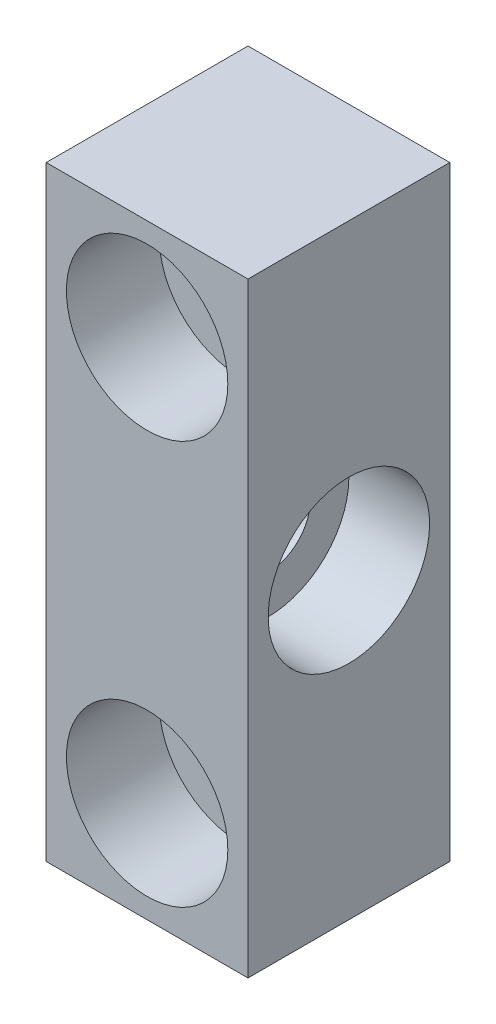
SolidWorks part; units mm, degrees
material "6061 合金"
ref_plane "前视基准面" through (0, 0, 0) normal (0, 0, 1) x (1, 0, 0)
ref_plane "上视基准面" through (0, 0, 0) normal (0, 1, 0) x (1, 0, 0)
ref_plane "右视基准面" through (0, 0, 0) normal (1, 0, 0) x (0, 0, -1)
sketch "草图1" plane through (0, 0, 0) normal (0, 0, 1) x (1, 0, 0)
  line L1 (-5, -15) -> (5, -15)
  line L2 (-5, -15) -> (-5, 15)
  line L3 (-5, 15) -> (5, 15)
  line L4 (5, -15) -> (5, 15)
  line L5 (-5, -15) -> (5, 15) construction
  line L6 (-5, 15) -> (5, -15) construction
  point P0 (0, 0)
  dimension "D1" = 10
  dimension "D2" = 30
extrude "凸台-拉伸1" add sketch "草图1" along normal blind 10
hole_wizard "打孔尺寸(%根据)内六角圆柱头螺钉的类型1" positions "草图3" profile "草图2" counterbore size "M4" standard "GB" end condition through all
sketch "草图3" plane through (0, 0, 10) normal (0, 0, 1) x (1, 0, 0)
  line L0 (5, 15) -> (-5, 15) construction
  point P0 (0, 10)
  point P2 (0, -10)
  dimension "D1" = 20
  dimension "D2" = 5
sketch "草图2" plane through (0, 10, 10) normal (1, 0, 0) x (0, -1, 0)
  line L0 (0, 0) -> (0, 10)
  line L1 (0, 10) -> (2.25, 10)
  line L3 (2.25, 10) -> (2.25, 4.6)
  line L4 (2.25, 4.6) -> (4, 4.6)
  line L5 (4, 4.6) -> (4, 0)
  line L7 (4, 0) -> (0, 0)
  line L11 (0, -6.35) -> (0, 107.95) construction
  dimension "通孔孔直径" = 4.5
  dimension "通孔孔深度" = 10
  dimension "柱形沉头孔直径" = 8
  dimension "柱形沉头孔深度" = 4.6
hole_wizard "Ø4.2 (4.2) 直径孔1" positions "草图5" profile "草图4" hole size "Ø4.2" standard "GB" end condition through all
sketch "草图5" plane through (5, 0, 0) normal (1, 0, 0) x (0, 0, -1)
  point P0 (-5, 0)
  dimension "D1" = 5
sketch "草图4" plane through (5, 0, 5) normal (0, 1, 0) x (0, 0, -1)
  line L0 (0, 0) -> (0, 10)
  line L1 (0, 10) -> (2.1, 10)
  line L2 (2.1, 10) -> (2.1, 0)
  line L5 (2.1, 0) -> (0, 0)
  line L11 (0, -6.35) -> (0, 107.95) construction
  dimension "通孔孔直径" = 4.2
  dimension "通孔孔深度" = 10
sketch "草图6" plane through (5, 0, 0) normal (1, 0, 0) x (0, 0, -1)
  circle A0 centre (-5, 0) radius 4
  dimension "D1" = 8
extrude "切除-拉伸1" cut sketch "草图6" against normal blind 4
